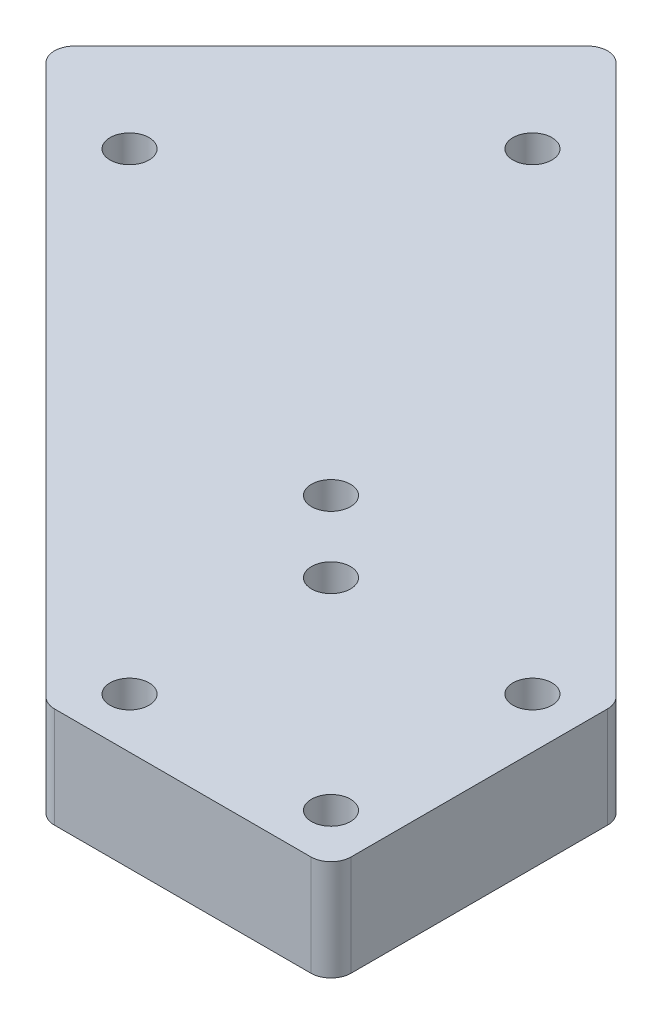
SolidWorks part; units mm, degrees
ref_plane "Front Plane" through (0, 0, 0) normal (0, 0, 1) x (1, 0, 0)
ref_plane "Top Plane" through (0, 0, 0) normal (0, 1, 0) x (1, 0, 0)
ref_plane "Right Plane" through (0, 0, 0) normal (1, 0, 0) x (0, 0, -1)
sketch "Sketch3" plane through (0, 0, 0) normal (0, 1, 0) x (1, 0, 0)
  line L1 (0, 0) -> (35.921, 0)
  line L2 (0, 0) -> (0, -35.921)
  line L3 (0, -35.921) -> (35.921, -35.921)
  line L4 (35.921, 0) -> (35.921, -35.921)
  dimension "D1" = 35.921
extrude "Boss-Extrude2" add sketch "Sketch3" along normal blind 12.7
ref_plane "Plane1" through (0, 0, 0) normal (-0.7071, 0, 0.7071) x (0.7071, 0, 0.7071)
sketch "Sketch4" plane through (0, 0, 0) normal (-0.7071, 0, 0.7071) x (0.7071, 0, 0.7071)
  line L0 (25.4, 12.7) -> (-50.8, 12.7)
  line L1 (0, 0) -> (-76.2, 0)
  line L2 (-50.8, 12.7) -> (-76.2, 12.7)
  line L3 (-76.2, 12.7) -> (-76.2, 0)
  line L4 (0, 0) -> (25.4, 0) construction
  line L5 (0, 0) -> (25.4, 0)
  line L6 (25.4, 0) -> (25.4, 12.7)
  dimension "D1" = 12.7
  dimension "D2" = 25.4
  dimension "D3" = 101.6
extrude "Boss-Extrude3" add sketch "Sketch4" along normal mid plane 50.8
hole_wizard "#8 Clearance Hole1" positions "Sketch5" profile "Sketch6" hole size "#8" standard "ANSI Inch" end condition through all
sketch "Sketch5" plane through (0, 0, 0) normal (0, -1, 0) x (-1, 0, 0)
  line L1 (-29.571, -29.571) -> (-4.171, -29.571)
  line L2 (-29.571, -29.571) -> (-29.571, -4.171)
  line L3 (-29.571, -4.171) -> (-4.171, -4.171)
  line L4 (-4.171, -29.571) -> (-4.171, -4.171)
  line L5 (-38.8909, -38.8909) -> (38.8909, 38.8909) construction
  line L6 (0, -35.921) -> (-35.921, -35.921) construction
  point P2 (-29.571, -29.571)
  point P3 (-4.171, -4.171)
  point P138 (-29.571, -4.171)
  point P139 (-4.171, -29.571)
  point P153 (4.8092, 4.8092)
  dimension "D1" = 6.35
  dimension "D2" = 25.4
  dimension "D3" = 12.7
sketch "Sketch6" plane through (29.571, 0, 29.571) normal (1, 0, 0) x (0, 0, -1)
  line L0 (0, 0) -> (0, 12.7)
  line L1 (0, 12.7) -> (2.4574, 12.7)
  line L2 (2.4574, 12.7) -> (2.4574, 0)
  line L5 (2.4574, 0) -> (0, 0)
  line L11 (0, -6.35) -> (0, 107.95) construction
  dimension "Thru Hole Dia." = 4.9149
  dimension "Thru Hole Depth" = 12.7
hole_wizard "#8 Clearance Hole2" positions "Sketch7" profile "Sketch8" hole size "#8" standard "ANSI Inch" end condition through all
sketch "Sketch7" plane through (0, 12.7, 0) normal (0, 1, 0) x (1, 0, 0)
  point P0 (-55.3543, 29.9581)
  point P3 (-29.9581, 55.3543)
sketch "Sketch8" plane through (-55.3543, 12.7, -29.9581) normal (1, 0, 0) x (0, 0, 1)
  line L0 (0, 0) -> (0, 12.7)
  line L1 (0, 12.7) -> (2.4574, 12.7)
  line L2 (2.4574, 12.7) -> (2.4574, 0)
  line L5 (2.4574, 0) -> (0, 0)
  line L11 (0, -6.35) -> (0, 107.95) construction
  dimension "Thru Hole Dia." = 4.9149
  dimension "Thru Hole Depth" = 12.7
fillet "Fillet1" radius 2.54 5 edges at (-35.921, 6.35, -71.842) (-71.842, 6.35, -35.921) (35.921, 6.35, 0) (35.921, 6.35, 35.921) (0, 6.35, 35.921)
equation "\"D1@Boss-Extrude3\"=sqr(2 )"
equation "\"D1@Sketch3\"=sqr(2)"
